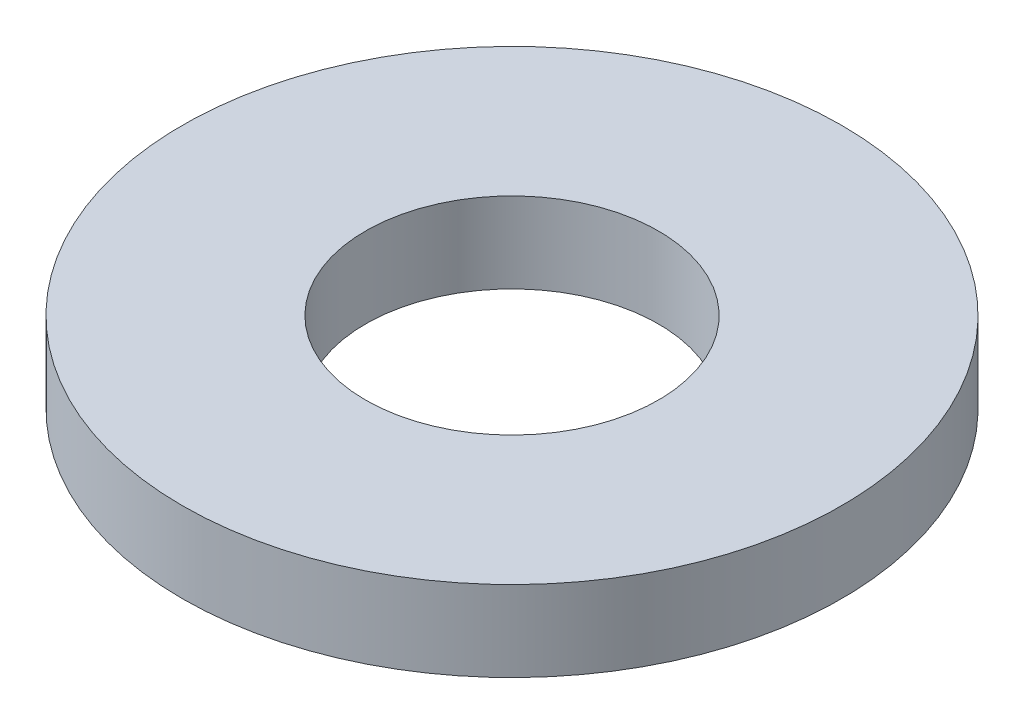
SolidWorks part; units mm, degrees
ref_plane "Front Plane" through (0, 0, 0) normal (0, 0, 1) x (1, 0, 0)
ref_plane "Top Plane" through (0, 0, 0) normal (0, 1, 0) x (1, 0, 0)
ref_plane "Right Plane" through (0, 0, 0) normal (1, 0, 0) x (0, 0, -1)
sketch "Sketch1" plane through (0, 0, 0) normal (0, 1, 0) x (1, 0, 0)
  circle A0 centre (0, 0) radius 45
  dimension "FLANGE_OD" = 90
extrude "Boss-Extrude1" add sketch "Sketch1" along normal blind 11
sketch "Sketch2" plane through (0, 0, 0) normal (0, 1, 0) x (1, 0, 0)
  circle A0 centre (0, 0) radius 20
  dimension "BORE_D" = 40
extrude "Cut-Extrude1" cut sketch "Sketch2" along normal through all
sketch "Sketch3" plane through (0, 11, 0) normal (0, 1, 0) x (1, 0, 0)
  circle A0 centre (0, 0) radius 14.1804 construction
  circle A1 centre (-14.1804, 0) radius 4.4162
  dimension "BOLT_D" = 8.8324
  dimension "BOLT_PCD" = 28.3608
extrude "Cut-Extrude2" cut sketch "Sketch3" against normal blind 10.6376 rebuild error yes
pattern_circular "CirPattern1" count 5 over 360 rebuild error yes
